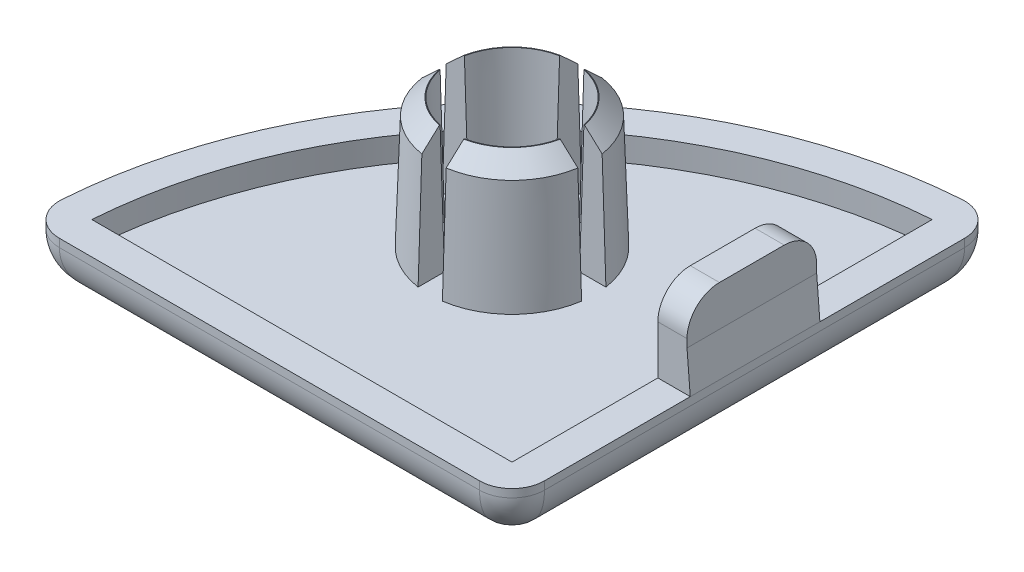
SolidWorks part; units mm, degrees
ref_plane "前视" through (0, 0, 0) normal (0, 0, 1) x (1, 0, 0)
ref_plane "上视" through (0, 0, 0) normal (0, 1, 0) x (1, 0, 0)
ref_plane "右视" through (0, 0, 0) normal (1, 0, 0) x (0, 0, -1)
sketch "草图1" plane through (0, 0, 0) normal (0, 1, 0) x (1, 0, 0)
  line L1 (-15, -15) -> (15, -15)
  line L4 (15, -15) -> (15, 15)
  line L5 (-15, -15) -> (15, 15) construction
  line L6 (-6.2132, 6.2132) -> (15, -15) construction
  arc A0 (15, 15) -> (-15, -15) centre (15, -15) ccw
  point P0 (0, 0)
  dimension "D3" = 30
  dimension "D1" = 30
  dimension "D2" = 30
extrude "凸台-拉伸1" add sketch "草图1" along normal blind 3.5
sketch "草图2" plane through (0, 3.5, 0) normal (0, 1, 0) x (1, 0, 0)
  line L4 (-12.9285, -13) -> (13, -13)
  line L5 (13, -13) -> (13, 12.9285)
  line L6 (-12.9285, -13) -> (13, -13)
  line L7 (13, -13) -> (13, 12.9285)
  arc A2 (13, 12.9285) -> (-12.9285, -13) centre (15, -15) ccw
  arc A3 (13, 12.9285) -> (-12.9285, -13) centre (15, -15) ccw
  dimension "D1" = 2
extrude "切除-拉伸1" cut sketch "草图2" against normal blind 1.5
fillet "圆角1" radius 2 3 edges at (15, 1.75, 15) (-15, 1.75, 15) (15, 1.75, -15)
fillet "圆角2" radius 3 6 edges at (14.4142, 0, 14.4142) (15, 0, 0.0358) (0.0358, 0, 15) (-6.2132, 0, -6.2132) (14.3628, 0, -14.3923) (-14.3923, 0, 14.3628)
sketch "草图3" plane through (0, 3.5, 0) normal (0, 1, 0) x (1, 0, 0)
  line L0 (13, -13) -> (13, 12.9285) construction
  line L1 (13, 4) -> (14.8, 4)
  line L2 (13, 4) -> (13, -4)
  line L3 (13, -4) -> (14.8, -4)
  line L4 (14.8, 4) -> (14.8, -4)
  dimension "D1" = 4
  dimension "D2" = 8
  dimension "D3" = 1.8
extrude "凸台-拉伸2" add sketch "草图3" along normal blind 5
sketch "草图5" plane through (0, 0, 4) normal (0, 0, 1) x (1, 0, 0)
  line L1 (15, 3.5) -> (14.8, 3.5)
  line L2 (14.8, 8.5) -> (14.8, 3.5) construction
  line L3 (15, 3.5) -> (15, 3) construction
  line L4 (14.8, 3.5) -> (14.8, 6)
  line L5 (14.8, 6) -> (15, 3.5)
  dimension "D1" = 2.5
extrude "凸台-拉伸3" add sketch "草图5" against normal up to surface (8 mm away) up to face at (14.125, 6.625, -4)
sketch "草图6" plane through (0, 2, 0) normal (0, 1, 0) x (1, 0, 0)
  circle A0 centre (0, 0) radius 5.1
  circle A1 centre (0, 0) radius 3.5
  dimension "D1" = 10.2
  dimension "D2" = 7
extrude "凸台-拉伸4" add sketch "草图6" along normal blind 8 draft 1.88
chamfer "倒角1" distance 1 angle 45 1 edges at (0, 10, 4.8374) first distance on face at (0, 10, 4.8374)
sketch "草图7" plane through (0, 2, 0) normal (0, 1, 0) x (1, 0, 0)
  line L1 (-0.75, -8.4649) -> (0.75, -8.4649)
  line L2 (-0.75, -8.4649) -> (-0.75, -0.75)
  line L3 (-0.75, 6.9577) -> (0.75, 6.9577)
  line L4 (0.75, -8.4649) -> (0.75, -0.75)
  line L7 (-6.8441, 0.75) -> (-0.75, 0.75)
  line L8 (-6.8441, 0.75) -> (-6.8441, -0.75)
  line L9 (-6.8441, -0.75) -> (-0.75, -0.75)
  line L10 (8.6795, 0.75) -> (8.6795, -0.75)
  line L13 (-0.75, 0.75) -> (-0.75, 6.9577)
  line L17 (0.75, 0.75) -> (0.75, 6.9577)
  line L19 (0.75, 0.75) -> (8.6795, 0.75)
  line L20 (0.75, -0.75) -> (8.6795, -0.75)
  point P0 (0, 0)
  point P6 (0, 0)
extrude "切除-拉伸2" cut sketch "草图7" along normal blind 10
fillet "圆角3" radius 2 2 edges at (13.9, 8.5, 4) (13.9, 8.5, -4)
